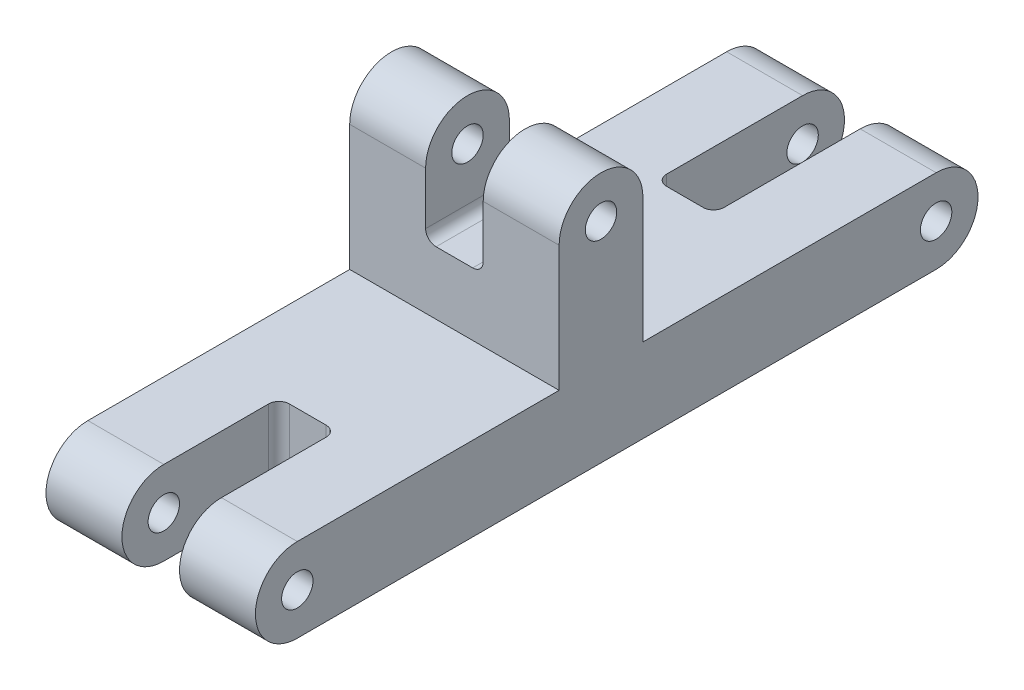
SolidWorks part; units mm, degrees
ref_plane "Alzado" through (0, 0, 0) normal (0, 0, 1) x (1, 0, 0)
ref_plane "Planta" through (0, 0, 0) normal (0, 1, 0) x (1, 0, 0)
ref_plane "Vista lateral" through (0, 0, 0) normal (1, 0, 0) x (0, 0, -1)
sketch "Croquis1" plane through (0, 0, 0) normal (1, 0, 0) x (0, 0, -1)
  line L0 (-15, 0) -> (15, 0) construction
  line L1 (-15, 4) -> (-21, 4) construction
  line L2 (-15, -4) -> (15, -4)
  line L3 (-13, 4) -> (15, 4)
  line L5 (-21, 4) -> (-21, 16)
  line L6 (-21, 16) -> (-13, 16) construction
  line L7 (-13, 4) -> (-13, 16)
  line L8 (-21, 4) -> (-46, 4)
  line L9 (-15, -4) -> (-46, -4)
  line L10 (-46, 4) -> (-46, -4) construction
  arc A0 (-15, 4) -> (-15, -4) centre (-15, 0) ccw construction
  arc A1 (15, -4) -> (15, 4) centre (15, 0) ccw
  circle A2 centre (15, 0) radius 1.5
  arc A3 (-13, 16) -> (-21, 16) centre (-17, 16) ccw
  circle A4 centre (-17, 16) radius 1.5
  circle A5 centre (-15, 0) radius 1.5 construction
  arc A6 (-46, 4) -> (-46, -4) centre (-46, 0) ccw
  circle A7 centre (-46, 0) radius 1.5
  point P3 (0, 0)
  dimension "D2" = 4
  dimension "D3" = 3
  dimension "D4" = 4
  dimension "D7" = 25
  dimension "D1" = 30
  dimension "D5" = 28
  dimension "D6" = 12
extrude "Saliente-Extruir1" add sketch "Croquis1" along normal mid plane 20
sketch "Croquis2" plane through (0, 0, 0) normal (1, 0, 0) x (0, 0, -1)
  line L0 (-21, 16) -> (-21, 4) construction
  line L1 (-21, 10) -> (-13, 10)
  line L2 (-21, 10) -> (-21, 20)
  line L3 (-21, 20) -> (-13, 20)
  line L4 (-13, 10) -> (-13, 20)
  line L5 (-13, 4) -> (-13, 16) construction
  line L11 (-46, -4) -> (15, -4) construction
  line L12 (15, 4) -> (-13, 4) construction
  line L13 (1, 4) -> (19, 4)
  line L14 (1, 4) -> (1, -4)
  line L15 (1, -4) -> (19, -4)
  line L16 (19, 4) -> (19, -4)
  line L18 (-35, 4) -> (-50, 4)
  line L19 (-35, 4) -> (-35, -4)
  line L20 (-35, -4) -> (-50, -4)
  line L21 (-50, 4) -> (-50, -4)
  line L22 (-46, -4) -> (15, -4) construction
  line L23 (-21, 4) -> (-46, 4) construction
  arc A0 (-13, 16) -> (-21, 16) centre (-17, 16) ccw construction
  arc A2 (15, -4) -> (15, 4) centre (15, 0) ccw construction
  arc A5 (-46, 4) -> (-46, -4) centre (-46, 0) ccw construction
  dimension "D5" = 15
  dimension "D1" = 10
  dimension "D3" = 18
extrude "Cortar-Extruir1" cut sketch "Croquis2" against normal mid plane 5.5
fillet "Redondeo1" radius 1 6 edges at (2.75, 0, 35) (-2.75, 0, 35) (2.75, 0, -1) (-2.75, 0, -1) (2.75, 10, 17) (-2.75, 10, 17)
